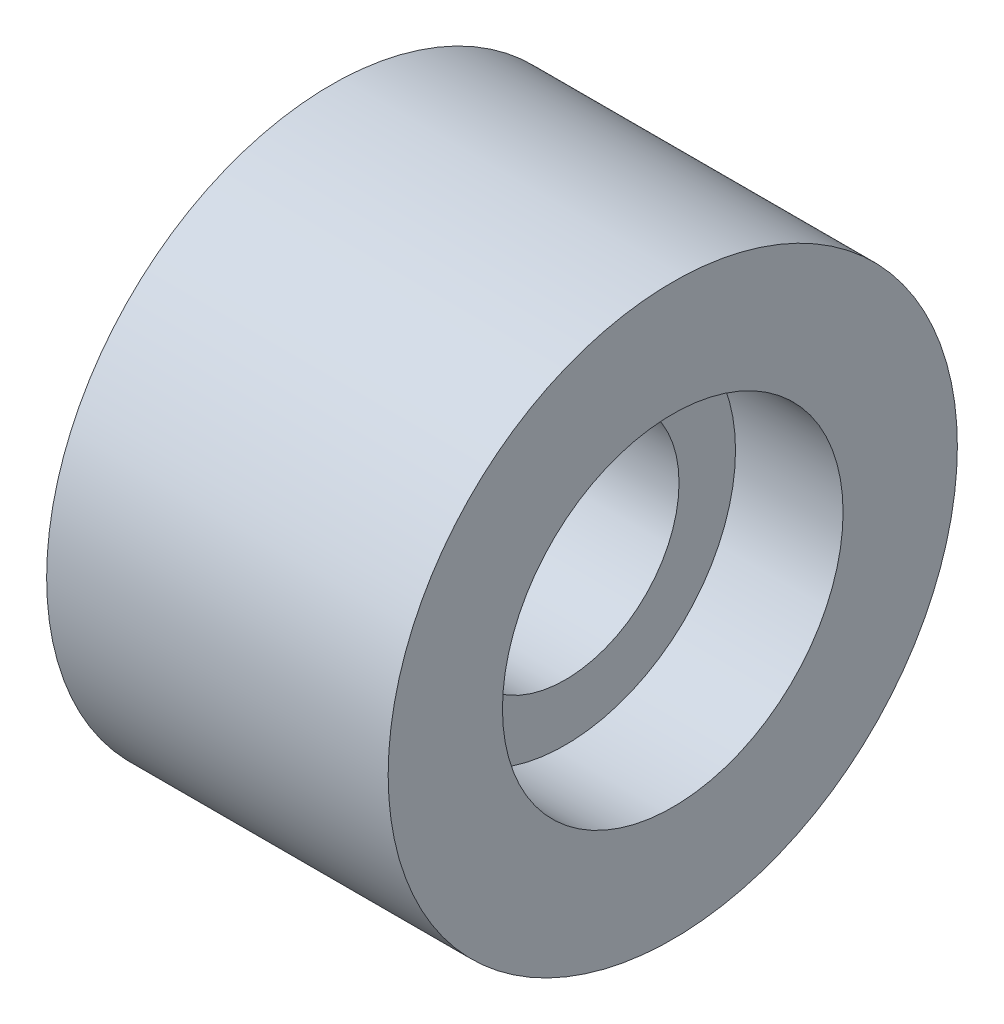
SolidWorks part; units mm, degrees
ref_plane "Front Plane" through (0, 0, 0) normal (0, 0, 1) x (1, 0, 0)
ref_plane "Top Plane" through (0, 0, 0) normal (0, 1, 0) x (1, 0, 0)
ref_plane "Right Plane" through (0, 0, 0) normal (1, 0, 0) x (0, 0, -1)
sketch "Sketch1" plane through (0, 0, 0) normal (1, 0, 0) x (0, 0, -1)
  circle A0 centre (0, 0) radius 9.5
  circle A1 centre (0, 0) radius 15.875
  circle A2 centre (0, 0) radius 6.35
  dimension "D1" = 19
  dimension "D2" = 31.75
  dimension "D3" = 12.7
extrude "Boss-Extrude1" add sketch "Sketch1" along normal blind 6 contours A1 A0 region at (0, 0, 15.426)
extrude "Boss-Extrude2" add sketch "Sketch1<3>" against normal blind 13.05 contours A0 A2 | A1 A0 region at (0, 0, 9.2313) region at (0, 0, 15.426)
sketch "Sketch1<3>" plane through (0, 0, 0) normal (1, 0, 0) x (0, 0, -1) same geometry as "Sketch1"
